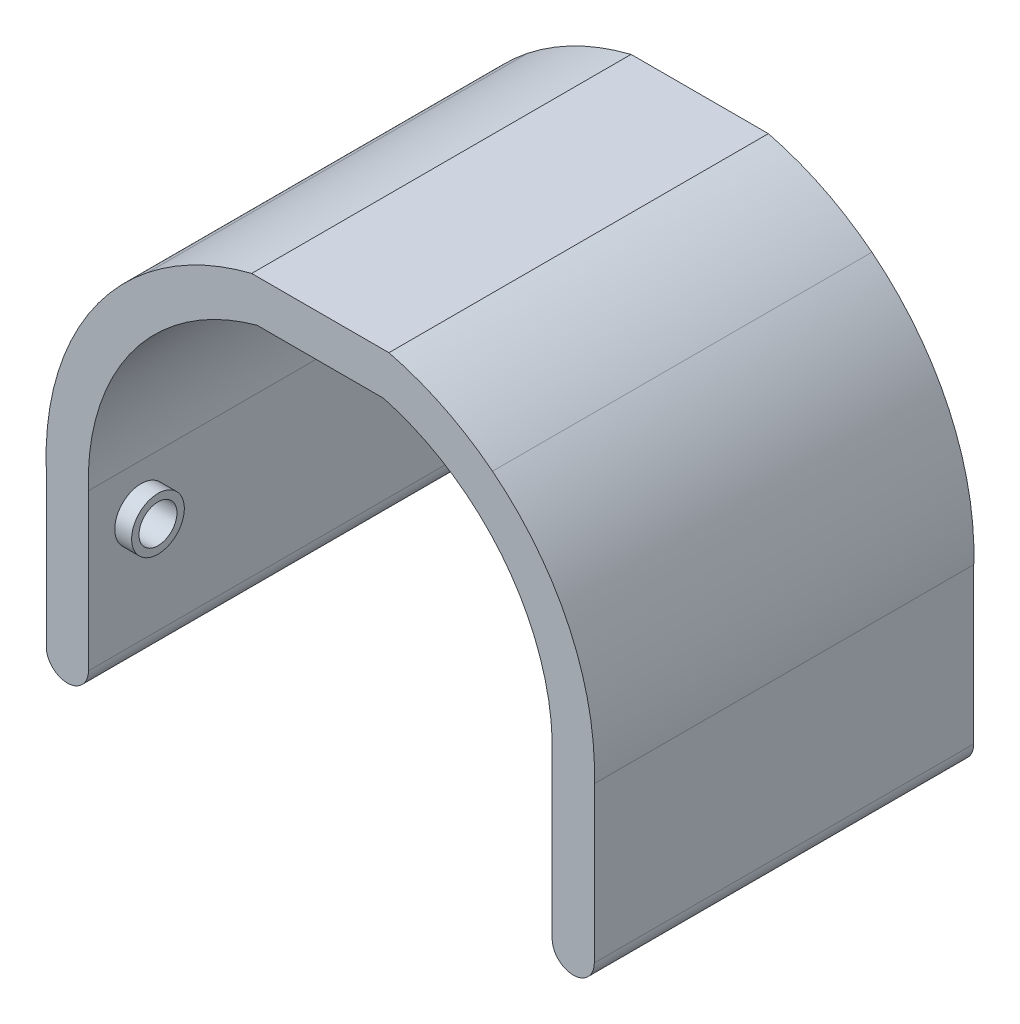
SolidWorks part; units mm, degrees
material "ABS PC"
ref_plane "Front Plane" through (0, 0, 0) normal (0, 0, 1) x (1, 0, 0)
ref_plane "Top Plane" through (0, 0, 0) normal (0, 1, 0) x (1, 0, 0)
ref_plane "Right Plane" through (0, 0, 0) normal (1, 0, 0) x (0, 0, -1)
sketch "Sketch1" plane through (0, 0, 0) normal (0, 0, 1) x (1, 0, 0)
  line L1 (-25, -25) -> (25, -25)
  line L2 (-25, -25) -> (-25, 25)
  line L3 (-25, 25) -> (25, 25)
  line L4 (25, -25) -> (25, 25)
  line L5 (-25, -25) -> (25, 25) construction
  line L6 (-25, 25) -> (25, -25) construction
  point P0 (0, 0)
  dimension "D1" = 50
  dimension "D2" = 50
extrude "Boss-Extrude1" add sketch "Sketch1" along normal blind 60
sketch "Sketch3" plane through (0, 0, 60) normal (0, 0, 1) x (1, 0, 0)
  line L0 (-25, 25) -> (-25, -25) construction
  line L1 (25, -25) -> (25, 25) construction
  line L6 (-25, 0) -> (-25, 25)
  line L7 (-25, 25) -> (25, 25)
  line L8 (25, 25) -> (25, 0)
  arc A0 (-25, 0) -> (25, 0) centre (0, 0) cw
  line M1 (25, -25) -> (25, 25)
  line M2 (25, 25) -> (-25, 25)
  line M3 (-25, 25) -> (-25, -25)
extrude "Cut-Extrude1" cut sketch "Sketch3" against normal up to surface (60 mm away) contours A0 L7 M3 | A0 M2 M1 region at (19.4158, 19.4158, 60) region at (-19.4158, 19.4158, 60) up to face at (0, 0, 0)
sketch "Sketch4" plane through (0, 0, 60) normal (0, 0, 1) x (1, 0, 0)
  line L0 (-25, -25) -> (25, -25) construction
  line L1 (25, -25) -> (25, 0) construction
  line L2 (-25, 0) -> (-25, -25) construction
  line L3 (-25, -25) -> (25, -25)
  line L4 (25, -25) -> (25, -11.0358)
  line L5 (-25, -11.0358) -> (-25, -25)
  line L6 (0, 22.8137) -> (0, -21.5771) construction
  arc A0 (-25, -11.0358) -> (-10, -25) centre (-11, -11.0358) ccw
  arc A1 (25, -11.0358) -> (10, -25) centre (11, -11.0358) cw
  arc A2 (-10, -25) -> (-8.5769, -23.0258) centre (-10, -23.5) ccw
  arc A3 (10, -25) -> (8.5769, -23.0258) centre (10, -23.5) cw
  arc A4 (-8.5769, -23.0258) -> (-7.9258, 4.0712) centre (29.372, -10.3814) cw
  arc A5 (8.5769, -23.0258) -> (7.9258, 4.0712) centre (-29.372, -10.3814) ccw
  arc A6 (-7.9258, 4.0712) -> (7.9258, 4.0712) centre (0, 1) cw
  arc A7 (25, 0) -> (-25, 0) centre (0, 0) ccw construction
  line M2 (25, -25) -> (25, 0)
  line M4 (-25, 0) -> (-25, -25)
  line M5 (-25, -25) -> (25, -25)
  dimension "D1" = 14
  dimension "D2" = 20
  dimension "D3" = 40
  dimension "D4" = 8.5
  dimension "D5" = 1
  dimension "D6" = 1.5
extrude "Cut-Extrude2" cut sketch "Sketch4" against normal up to surface (60 mm away) contours A6 A4 A2 A3 A5 M5 | A0 M4 M5 | A1 M2 M5 region at (0, -8.8337, 60) region at (-21.9135, -21.873, 60) region at (21.9135, -21.873, 60) up to face at (0, -6.25, 0)
sketch "Sketch5" plane through (0, 0, 60) normal (0, 0, 1) x (1, 0, 0)
  line L0 (-7.9258, 4.0712) -> (-12.8794, 4.0712)
  line L1 (-12.8794, 4.0712) -> (-12.8794, -5.9288)
  line L2 (-12.8794, -5.9288) -> (-10.3794, -5.9288)
  line L3 (7.9258, 4.0712) -> (12.8794, 4.0712)
  line L4 (12.8794, 4.0712) -> (12.8794, -5.9288)
  line L5 (12.8794, -5.9288) -> (10.3794, -5.9288)
  arc A0 (8.5769, -23.0258) -> (7.9258, 4.0712) centre (-29.372, -10.3814) ccw construction
  arc A1 (-7.9258, 4.0712) -> (-8.5769, -23.0258) centre (29.372, -10.3814) ccw construction
  arc A2 (10.3794, -5.9288) -> (7.9258, 4.0712) centre (-29.372, -10.3814) ccw
  arc A3 (-7.9258, 4.0712) -> (-10.3794, -5.9288) centre (29.372, -10.3814) ccw
  dimension "D1" = 10
  dimension "D2" = 10
  dimension "D3" = 2.5
  dimension "D4" = 2.5
extrude "Cut-Extrude3" cut sketch "Sketch5" against normal blind 10 flip side to cut
sketch "Sketch6" plane through (0, 0, 0) normal (0, 0, -1) x (-1, 0, 0)
  line L1 (12.8794, 4.0712) -> (12.8794, -5.9288) construction
  line L4 (-12.8794, 4.0712) -> (-12.8794, -5.9288) construction
  line L7 (12.8794, 3.0712) -> (12.8794, -4.9288)
  line L10 (-12.8794, 3.0712) -> (-12.8794, -4.9288)
  line L14 (-15.8794, 5.0712) -> (-15.8794, -6.9324)
  line L16 (12.8794, 3.0712) -> (12.8794, 6.0712)
  line L17 (0, 26.9146) -> (0, -26.5291) construction
  line L18 (15.8794, 5.0712) -> (15.8794, -6.9324)
  line L19 (12.8794, 6.0712) -> (14.8794, 6.0712)
  line L20 (-12.8794, 3.0712) -> (-12.8794, 6.0712)
  line L21 (-12.8794, 6.0712) -> (-14.8794, 6.0712)
  line L22 (-12.8794, -4.9288) -> (-12.8794, -7.9324)
  line L23 (-12.8794, -7.9324) -> (-14.8794, -7.9324)
  line L24 (12.8794, -4.9288) -> (12.8794, -7.9324)
  line L25 (12.8794, -7.9324) -> (14.8794, -7.9324)
  arc A1 (-7.9258, 4.0712) -> (-10.3794, -5.9288) centre (29.372, -10.3814) ccw construction
  arc A4 (-7.9258, 4.0712) -> (-8.5769, -23.0258) centre (29.372, -10.3814) ccw construction
  arc A5 (-10.3794, -5.9288) -> (-8.5769, -23.0258) centre (29.372, -10.3814) ccw
  arc A6 (-10.553, -7.9324) -> (-10.3794, -5.9288) centre (29.372, -10.3814) cw
  arc A11 (-15.8794, -6.9324) -> (-14.8794, -7.9324) centre (-14.8794, -6.9324) ccw
  arc A12 (-14.8794, 6.0712) -> (-15.8794, 5.0712) centre (-14.8794, 5.0712) ccw
  arc A15 (15.8794, -6.9324) -> (14.8794, -7.9324) centre (14.8794, -6.9324) cw
  arc A17 (14.8794, 6.0712) -> (15.8794, 5.0712) centre (14.8794, 5.0712) cw
  point P34 (-15.8794, -7.9324)
  point P37 (-15.8794, 6.0712)
  arc M9 (8.5769, -23.0258) -> (10, -25) centre (10, -23.5) ccw
  arc M10 (12, -25) -> (25, -11.0358) centre (11, -11.0358) ccw
  line M11 (25, -11.0358) -> (25, 0)
  arc M12 (25, 0) -> (-25, 0) centre (0, 0) ccw
  line M13 (-25, 0) -> (-25, -11.0358)
  arc M14 (-25, -11.0358) -> (-12, -25) centre (-11, -11.0358) ccw
  arc M15 (-10, -25) -> (-8.5769, -23.0258) centre (-10, -23.5) ccw
  arc M16 (-8.5769, -23.0258) -> (-7.9258, 4.0712) centre (29.372, -10.3814) cw
  arc M17 (-7.9258, 4.0712) -> (7.9258, 4.0712) centre (0, 1) cw
  arc M18 (7.9258, 4.0712) -> (8.5769, -23.0258) centre (-29.372, -10.3814) cw
  line M20 (-12, -25) -> (-10, -25)
  line M21 (10, -25) -> (12, -25)
  dimension "D1" = 3
extrude "Cut-Extrude4" cut sketch "Sketch6" against normal blind 10 contours L17 L14 L10 M12 M13 M14 M20 M15 M16 M17 | L17 L7 L18 M12 M17 M18 M9 M21 M10 M11 | L10 M16 | L7 M18 region at (-17.2824, 17.2824, 0) region at (0.559, 17.25, 0)
fillet "Fillet1" radius 1 4 edges at (12.8794, 4.0712, 55) (12.8794, -5.9288, 55) (-12.8794, -5.9288, 55) (-12.8794, 4.0712, 55)
sketch "Sketch7" plane through (-12.8794, 0, 0) normal (-1, 0, 0) x (0, 0, 1)
  line L0 (55, 3.0712) -> (55, -4.9288) construction
  line L1 (60, 3.0712) -> (50, 3.0712) construction
  line L2 (50, -4.9288) -> (60, -4.9288) construction
  line L3 (60, -0.9288) -> (50, -0.9288) construction
  line L4 (60, -5.9288) -> (60, 4.0712) construction
  line L5 (50, 3.0712) -> (50, -4.9288) construction
  circle A0 centre (55, -0.9288) radius 2
  dimension "D1" = 4
extrude "Boss-Extrude2" add sketch "Sketch7" along normal blind 2
sketch "Sketch8" plane through (12.8794, 0, 0) normal (1, 0, 0) x (0, 0, -1)
  line L0 (-55, 3.0712) -> (-55, -4.9288) construction
  line L1 (-50, 3.0712) -> (-60, 3.0712) construction
  line L2 (-60, -4.9288) -> (-50, -4.9288) construction
  line L3 (-60, -0.9288) -> (-50, -0.9288) construction
  line L4 (-60, 4.0712) -> (-60, -5.9288) construction
  line L5 (-50, -4.9288) -> (-50, 3.0712) construction
  circle A0 centre (-55, -0.9288) radius 2
  dimension "D1" = 4
extrude "Boss-Extrude3" add sketch "Sketch8" along normal blind 2
sketch "Sketch9" plane through (12.8794, 0, 0) normal (-1, 0, 0) x (0, 0, 1)
  line L0 (5, 5.0712) -> (5, -6.9324) construction
  line L1 (10, 5.0712) -> (0, 5.0712) construction
  line L2 (10, -6.9324) -> (0, -6.9324) construction
  line L3 (0, -0.9306) -> (10, -0.9306) construction
  line L4 (0, 5.0712) -> (0, -6.9324) construction
  line L5 (10, 5.0712) -> (10, -6.9324) construction
  circle A0 centre (5, -0.9306) radius 2.25
  dimension "D1" = 4.5
extrude "Cut-Extrude5" cut sketch "Sketch9" against normal blind 2
sketch "Sketch10" plane through (-12.8794, 0, 0) normal (1, 0, 0) x (0, 0, -1)
  line L0 (-5, 5.0712) -> (-5, -6.9324) construction
  line L1 (-10, 5.0712) -> (0, 5.0712) construction
  line L2 (-10, -6.9324) -> (0, -6.9324) construction
  line L3 (-10, -0.9306) -> (0, -0.9306) construction
  line L4 (-10, 5.0712) -> (-10, -6.9324) construction
  line L5 (0, 5.0712) -> (0, -6.9324) construction
  circle A0 centre (-5, -0.9306) radius 2.25
  dimension "D1" = 4.5
extrude "Cut-Extrude6" cut sketch "Sketch10" against normal blind 2
fillet "Fillet2" radius 1 4 edges at (-12.8794, -7.9324, 5) (-12.8794, 6.0712, 5) (12.8794, -7.9324, 5) (12.8794, 6.0712, 5)
sketch "Sketch11" plane through (0, 0, 0) normal (1, 0, 0) x (0, 0, -1)
  line L0 (-10, 0) -> (-10, 25) construction
  line L1 (-10, 5.0712) -> (0, 5.0712) construction
  line L2 (0, 5.0712) -> (0, -6.9324) construction
  line L3 (-10, 0) -> (-10, 25)
  line L4 (-10, 5.0712) -> (0, 5.0712)
  line L5 (0, 5.0712) -> (0, -6.9324)
  line L6 (-50, 25) -> (-50, 0) construction
  line L7 (-50, 25) -> (-50, 0)
  line L8 (-30, 12.5) -> (-30, 36.2918) construction
  line L9 (-50, 25) -> (-10, 25)
  line L10 (-10, 25) -> (-10, 12.5)
  line L11 (-50, 25) -> (-50, 12.5)
  arc A0 (-10, 12.5) -> (-30, 32.5) centre (-30, 12.5) ccw
  spline S0 degree 3 poles (-50, 12.5) (-41.6701, 27.9801) (-18.3299, 27.9801) (-10, 12.5) knots 0 0 0 0 1 1 1 1
  dimension "D2" = 48.6
  dimension "D1" = 4.5
extrude "Cut-Extrude7" cut sketch "Sketch11" along normal up to surface and the other way up to surface contours S0 L8 L9 L7 | L8 S0 A0 L9 | A0 L3 L9 region at (0, 21.9477, 11.2872) region at (0, 21.5983, 16.9845) region at (0, 21.671, 44.2013) up to face at (0, 12.5, 30) other way up to face at (0, 12.5, 30)
sketch "Sketch12" plane through (0, 0, 50) normal (0, 0, 1) x (1, 0, 0)
  line L0 (6.9394, 26.6101) -> (-6.9393, 26.6101)
  line L1 (27.5, -11.0358) -> (27.5, 0)
  line L4 (-27.5, 0) -> (-27.5, -11.0358)
  line L5 (-27.5, -11.0358) -> (-27.5, -13.5358)
  line L6 (27.5, -11.0358) -> (27.5, -13.5358)
  line L9 (6.611, 24.1101) -> (-6.611, 24.1101) construction
  line L10 (-12, -25) -> (-10, -25) construction
  line L11 (10, -25) -> (12, -25) construction
  line L12 (25, -11.0358) -> (25, 0) construction
  line L13 (-25, 0) -> (-25, -11.0358) construction
  line L14 (6.611, 24.1101) -> (-6.6109, 24.1101)
  line L15 (-12, -25) -> (-10, -25)
  line L16 (10, -25) -> (12, -25)
  line L17 (25, -11.0358) -> (25, 0)
  line L18 (-25, 0) -> (-25, -11.0358)
  line L19 (21.6506, 12.5) -> (-21.6506, 12.5) construction
  line L20 (-12.0857, -27.5) -> (-10, -27.5) construction
  line L21 (10, -27.5) -> (12.0857, -27.5) construction
  arc A0 (-23.8157, 13.75) -> (-6.9393, 26.6101) centre (0, 0) cw
  arc A1 (6.9394, 26.6101) -> (23.8157, 13.75) centre (0, 0) cw
  arc A2 (27.5, 0) -> (23.8157, 13.75) centre (0, 0) ccw
  arc A12 (-23.8157, 13.75) -> (-27.5, 0) centre (0, 0) ccw
  arc A30 (-25, -11.0358) -> (-12, -25) centre (-11, -11.0358) ccw construction
  arc A31 (-10, -25) -> (-8.5769, -23.0258) centre (-10, -23.5) ccw construction
  arc A32 (-10.3794, -5.9288) -> (-8.5769, -23.0258) centre (29.372, -10.3814) ccw construction
  arc A33 (-7.9258, 4.0712) -> (-10.3794, -5.9288) centre (29.372, -10.3814) ccw construction
  arc A34 (7.9258, 4.0712) -> (-7.9258, 4.0712) centre (0, 1) ccw construction
  arc A35 (10.3794, -5.9288) -> (7.9258, 4.0712) centre (-29.372, -10.3814) ccw construction
  arc A36 (8.5769, -23.0258) -> (10.3794, -5.9288) centre (-29.372, -10.3814) ccw construction
  arc A37 (8.5769, -23.0258) -> (10, -25) centre (10, -23.5) ccw construction
  arc A38 (12, -25) -> (25, -11.0358) centre (11, -11.0358) ccw construction
  arc A39 (25, 0) -> (21.6506, 12.5) centre (0, 0) ccw construction
  arc A40 (-21.6506, 12.5) -> (-25, 0) centre (0, 0) ccw construction
  arc A41 (-25, -11.0358) -> (-12, -25) centre (-11, -11.0358) ccw
  arc A42 (-10, -25) -> (-8.5769, -23.0258) centre (-10, -23.5) ccw
  arc A43 (-10.3794, -5.9288) -> (-8.5769, -23.0258) centre (29.372, -10.3814) ccw
  arc A44 (-7.9258, 4.0712) -> (-10.3794, -5.9288) centre (29.372, -10.3814) ccw
  arc A45 (7.9258, 4.0712) -> (-7.9258, 4.0712) centre (0, 1) ccw
  arc A46 (10.3794, -5.9288) -> (7.9258, 4.0712) centre (-29.372, -10.3814) ccw
  arc A47 (8.5769, -23.0258) -> (10.3794, -5.9288) centre (-29.372, -10.3814) ccw
  arc A48 (8.5769, -23.0258) -> (10, -25) centre (10, -23.5) ccw
  arc A49 (12, -25) -> (25, -11.0358) centre (11, -11.0358) ccw
  arc A50 (25, 0) -> (21.6506, 12.5) centre (0, 0) ccw
  arc A51 (-21.6506, 12.5) -> (-25, 0) centre (0, 0) ccw
  arc A52 (-21.6506, 12.5) -> (-6.6109, 24.1101) centre (0, 0) cw
  arc A53 (6.611, 24.1101) -> (21.6506, 12.5) centre (0, 0) cw
  arc A54 (-27.5, -11.0358) -> (-12.0857, -27.5) centre (-11, -11.0358) ccw construction
  arc A55 (-10, -27.5) -> (-6.2051, -22.2356) centre (-10, -23.5) ccw construction
  arc A56 (-7.895, -6.2071) -> (-6.2051, -22.2356) centre (29.372, -10.3814) ccw construction
  arc A57 (-5.5947, 3.1679) -> (-7.895, -6.2071) centre (29.372, -10.3814) ccw construction
  arc A58 (5.5947, 3.1679) -> (-5.5947, 3.1679) centre (0, 1) ccw construction
  arc A59 (7.895, -6.2071) -> (5.5947, 3.1679) centre (-29.372, -10.3814) ccw construction
  arc A60 (6.2051, -22.2356) -> (7.895, -6.2071) centre (-29.372, -10.3814) ccw construction
  arc A61 (6.2051, -22.2356) -> (10, -27.5) centre (10, -23.5) ccw construction
  arc A62 (12.0857, -27.5) -> (27.5, -11.0358) centre (11, -11.0358) ccw construction
  dimension "D1" = 25
  dimension "D3" = 2.5
sketch "Sketch13" plane through (0, 0, 50) normal (0, 0, 1) x (1, 0, 0)
  line L0 (-27.5, 0) -> (-27.5, -18.5)
  line L1 (0, -25.3315) -> (0, 35.0065) construction
  line L2 (-7.5, 27) -> (7.5, 27)
  line L3 (27.5, 0) -> (27.5, -18.5)
  line L4 (-35.1274, 0) -> (35.1872, 0) construction
  line L5 (32.5, -0.0893) -> (32.5, -18.5)
  line L6 (-8.14, 32) -> (8.14, 32)
  line L7 (-32.5, -0.0893) -> (-32.5, -18.5)
  arc A0 (-27.5, 0) -> (-17.3247, 22.0443) centre (-0.7, 1) cw
  arc A1 (-17.3247, 22.0443) -> (-7.5, 27) centre (-0.2776, 0.4654) cw
  arc A2 (-23.8157, 13.75) -> (-27.5, 0) centre (0, 0) ccw construction
  arc A3 (7.5, 27) -> (17.3247, 22.0443) centre (0.2776, 0.4654) cw
  arc A4 (20.4241, 25.9677) -> (32.5, -0.0893) centre (0.7, 1) cw
  arc A5 (17.3247, 22.0443) -> (27.5, 0) centre (0.7, 1) cw
  arc A6 (8.14, 32) -> (20.4241, 25.9677) centre (0.2776, 0.4654) cw
  arc A7 (-20.4241, 25.9677) -> (-8.14, 32) centre (-0.2776, 0.4654) cw
  arc A8 (-32.5, -0.0893) -> (-20.4241, 25.9677) centre (-0.7, 1) cw
  arc A9 (-27.5, -18.5) -> (-32.5, -18.5) centre (-30, -18.5) cw
  arc A10 (27.5, -18.5) -> (32.5, -18.5) centre (30, -18.5) ccw
  dimension "D1" = 15
  dimension "D2" = 27.5
  dimension "D3" = 27.5
  dimension "D6" = 0.7
  dimension "D9" = 18.5
  dimension "D4" = 27
  dimension "D5" = 27.5
  dimension "D7" = 1
  dimension "D8" = 5
extrude "Boss-Extrude4" add sketch "Sketch13" against normal blind 10 and the other way blind 35 separate body
sketch "Sketch14" plane through (-25, 0, 0) normal (-1, 0, 0) x (0, 0, 1)
  line L0 (50, 0) -> (50, -11.0358) construction
  line L1 (10, -11.0358) -> (50, -11.0358) construction
  line L2 (10, -11.0358) -> (10, 0) construction
  line L3 (10, 0) -> (50, 0) construction
  line L4 (50, 0) -> (50, -11.0358)
  line L5 (10, -11.0358) -> (50, -11.0358)
  line L6 (10, -11.0358) -> (10, 0)
  line L7 (10, 0) -> (50, 0)
  line L8 (30, 0) -> (30, -11.0358) construction
  line L9 (10, -5.5179) -> (50, -5.5179) construction
  line L10 (42.5, 0) -> (42.5, -11.0358) construction
  line L11 (46.25, 0) -> (46.25, -11.0358) construction
  circle A0 centre (46.25, -5.5179) radius 2
  dimension "D3" = 4
  dimension "D1" = 7.5
  dimension "D2" = 3.75
extrude "Boss-Extrude5" add sketch "Sketch14" along normal blind 0.1 contours A0
sketch "Sketch15" plane through (-32.5, 0, 0) normal (-1, 0, 0) x (0, 0, 1)
  line L0 (30, 0) -> (30, -11.0358) construction
  line L4 (10, 0) -> (10, -11.0358)
  line L5 (10, -11.0358) -> (50, -11.0358)
  line L6 (50, -11.0358) -> (50, 0)
  line L7 (50, 0) -> (10, 0)
  line L8 (10, 0) -> (10, -11.0358)
  line L9 (10, -11.0358) -> (50, -11.0358)
  line L10 (50, -11.0358) -> (50, 0)
  line L11 (50, 0) -> (10, 0)
  circle A0 centre (46.25, -5.5179) radius 2.25
  circle A1 centre (46.25, -5.5179) radius 2
  circle A2 centre (46.25, -5.5179) radius 2
  circle A3 centre (46.25, -5.5179) radius 3
  dimension "D3" = 4.5
  dimension "D4" = 6
  dimension "D1" = 0
  dimension "D2" = 0
extrude "Boss-Extrude6" add sketch "Sketch15" against normal blind 7 contours A3 A0
sketch "Sketch16" plane through (-27.5, 0, 0) normal (1, 0, 0) x (0, 0, -1)
  circle A0 centre (-46.25, -5.5179) radius 2.25 construction
  circle A1 centre (-46.25, -5.5179) radius 2.25
extrude "Cut-Extrude8" cut sketch "Sketch16" against normal blind 2
sketch "Sketch17" plane through (-14.8794, 0, 0) normal (-1, 0, 0) x (0, 0, 1)
  line L1 (50, -5.9288) -> (60, -5.9288)
  line L2 (50, -5.9288) -> (50, 4.0712)
  line L3 (50, 4.0712) -> (60, 4.0712)
  line L4 (60, -5.9288) -> (60, 4.0712)
extrude "Cut-Extrude9" cut sketch "Sketch17" against normal up to surface (29.7589 mm away) up to face at (14.8794, 1.0712, 55)
sketch "Sketch18" plane through (-15.8794, 0, 0) normal (-1, 0, 0) x (0, 0, 1)
  line L1 (0, 6.0712) -> (10, 6.0712)
  line L2 (0, 6.0712) -> (0, -7.9324)
  line L3 (0, -7.9324) -> (10, -7.9324)
  line L4 (10, 6.0712) -> (10, -7.9324)
extrude "Cut-Extrude10" cut sketch "Sketch18" against normal up to surface (31.7589 mm away) up to face at (15.8794, -0.9306, 5)
sketch "Sketch19" plane through (25, 0, 0) normal (1, 0, 0) x (0, 0, -1)
  line L4 (-10, -11.0358) -> (-10, 0)
  line L5 (-10, 0) -> (-50, 0)
  line L6 (-50, 0) -> (-50, -11.0358)
  line L7 (-50, -11.0358) -> (-10, -11.0358)
  line L8 (-10, -11.0358) -> (-10, 0)
  line L9 (-10, 0) -> (-50, 0)
  line L10 (-50, 0) -> (-50, -11.0358)
  line L11 (-50, -11.0358) -> (-10, -11.0358)
  circle A1 centre (-46.25, -5.5179) radius 2
  circle A2 centre (-46.25, -5.5179) radius 2
  dimension "D1" = 0
  dimension "D2" = 0
sketch "Sketch20" plane through (32.5, 0, 0) normal (1, 0, 0) x (0, 0, -1)
  line L0 (-62.5, -0.0893) -> (-62.5, -18.5) construction
  line L1 (-85, -0.0893) -> (-40, -0.0893) construction
  line L2 (-85, -18.5) -> (-40, -18.5) construction
  circle A0 centre (-46.25, -5.5179) radius 3 construction
  circle A1 centre (-46.25, -5.5179) radius 2.25 construction
  circle A2 centre (-46.25, -5.5179) radius 3
  circle A3 centre (-46.25, -5.5179) radius 2.25
  circle A4 centre (-78.75, -5.5179) radius 3
  circle A5 centre (-78.75, -5.5179) radius 2.25
  dimension "D1" = 5.4286
extrude "Boss-Extrude8" add sketch "Sketch20" against normal blind 7
sketch "Sketch21" plane through (27.5, 0, 0) normal (-1, 0, 0) x (0, 0, 1)
  circle A0 centre (46.25, -5.5179) radius 2.25 construction
  circle A1 centre (46.25, -5.5179) radius 2.25
extrude "Cut-Extrude11" cut sketch "Sketch21" against normal blind 4
sketch "Sketch22" plane through (0, 0, 10) normal (0, 0, -1) x (-1, 0, 0)
  line L0 (-12, -25) -> (-10, -25) construction
  line L1 (10, -25) -> (12, -25) construction
  line L2 (25, -11.0358) -> (25, 0) construction
  line L3 (-25, -11.0358) -> (-25, 0) construction
  line L4 (-12, -25) -> (-10, -25)
  line L5 (10, -25) -> (12, -25)
  line L6 (25, -11.0358) -> (25, 0)
  line L7 (-25, -11.0358) -> (-25, 0)
  line L8 (-25, 0) -> (-25, 10.5653)
  line L9 (25.2505, 0) -> (25.2505, -10.33)
  line L10 (25.2505, -10.33) -> (25.2505, -25.8902)
  line L11 (25.2505, -25.8902) -> (-25, -25.8902)
  line L12 (-25, -25.8902) -> (-25, -11.0358)
  arc A0 (-25, 10.5653) -> (13.9273, 22.2696) centre (-0.3638, -0.786) cw
  arc A1 (13.9273, 22.2696) -> (25.2505, 0) centre (1.2433, 1.8067) cw
  arc A2 (-25, -11.0358) -> (-12, -25) centre (-11, -11.0358) ccw construction
  arc A3 (12, -25) -> (25, -11.0358) centre (11, -11.0358) ccw construction
  arc A4 (-25, -11.0358) -> (-12, -25) centre (-11, -11.0358) ccw
  arc A5 (12, -25) -> (25, -11.0358) centre (11, -11.0358) ccw
  arc M9 (-8.5769, -23.0258) -> (-7.9258, 4.0712) centre (29.372, -10.3814) cw
  arc M10 (-7.9258, 4.0712) -> (7.9258, 4.0712) centre (0, 1) cw
  arc M11 (7.9258, 4.0712) -> (8.5769, -23.0258) centre (-29.372, -10.3814) cw
  arc M12 (8.5769, -23.0258) -> (10, -25) centre (10, -23.5) ccw
  line M13 (10, -25) -> (12, -25)
  arc M14 (12, -25) -> (25, -11.0358) centre (11, -11.0358) ccw
  line M15 (25, -11.0358) -> (25, 0)
  arc M16 (25, 0) -> (21.6506, 12.5) centre (0, 0) ccw
  line M17 (21.6506, 12.5) -> (-21.6506, 12.5)
  arc M18 (-21.6506, 12.5) -> (-25, 0) centre (0, 0) ccw
  line M19 (-25, 0) -> (-25, -11.0358)
  arc M20 (-25, -11.0358) -> (-12, -25) centre (-11, -11.0358) ccw
  line M21 (-12, -25) -> (-10, -25)
  arc M22 (-10, -25) -> (-8.5769, -23.0258) centre (-10, -23.5) ccw
  dimension "D1" = 27.1255
  dimension "D4" = 24.0751
  dimension "D2" = 50.2505
  dimension "D3" = 25.8902
  dimension "D5" = 1.8067
  dimension "D6" = 1.2433
  dimension "D7" = 0.786
extrude "Cut-Extrude12" cut sketch "Sketch22" against normal up to surface (40 mm away) contours A1 A0 L8 L12 L11 L10 L9 M18 M17 M16 M15 M14 M13 M12 M11 M10 M9 M22 M21 M20 | M22 M9 M10 M11 M12 M13 M14 M15 M16 M17 M18 M19 M20 M21 region at (20.7895, -20.1493, 10) region at (0.1114, 0.003, 10) up to face at (0, -9.6315, 50)
sketch "Sketch23" plane through (27.5, 0, 0) normal (-1, 0, 0) x (0, 0, 1)
  circle A1 centre (78.75, -5.5179) radius 2.25
  circle A2 centre (78.75, -5.5179) radius 2.25
  dimension "D1" = 0
extrude "Cut-Extrude13" cut sketch "Sketch23" against normal blind 4
sketch "Sketch24" plane through (-29.5, 0, 0) normal (1, 0, 0) x (0, 0, -1)
  circle A1 centre (-46.25, -5.5179) radius 2.25
  circle A2 centre (-46.25, -5.5179) radius 2.25
  dimension "D1" = 0
extrude "Cut-Extrude14" cut sketch "Sketch24" against normal blind 2
sketch "Sketch25" plane through (-32.5, 0, 0) normal (-1, 0, 0) x (0, 0, 1)
  line L0 (78.75, -0.0893) -> (78.75, -18.5) construction
  line L1 (85, -0.0893) -> (40, -0.0893) construction
  line L2 (85, -18.5) -> (40, -18.5) construction
  line L3 (85, -0.0893) -> (85, -18.5) construction
  line L4 (40, -5.5179) -> (85, -5.5179) construction
  line L5 (40, -0.0893) -> (40, -18.5) construction
  circle A0 centre (78.75, -5.5179) radius 2.25
  circle A1 centre (78.75, -5.5179) radius 3.125
  dimension "D3" = 4.5
  dimension "D4" = 6.25
  dimension "D1" = 6.25
  dimension "D2" = 5.4286
extrude "Boss-Extrude9" add sketch "Sketch25" against normal blind 7
sketch "Sketch26" plane through (-27.5, 0, 0) normal (1, 0, 0) x (0, 0, -1)
  circle A1 centre (-78.75, -5.5179) radius 2.25
  circle A2 centre (-78.75, -5.5179) radius 2.25
  dimension "D1" = 0
extrude "Cut-Extrude15" cut sketch "Sketch26" against normal blind 4
